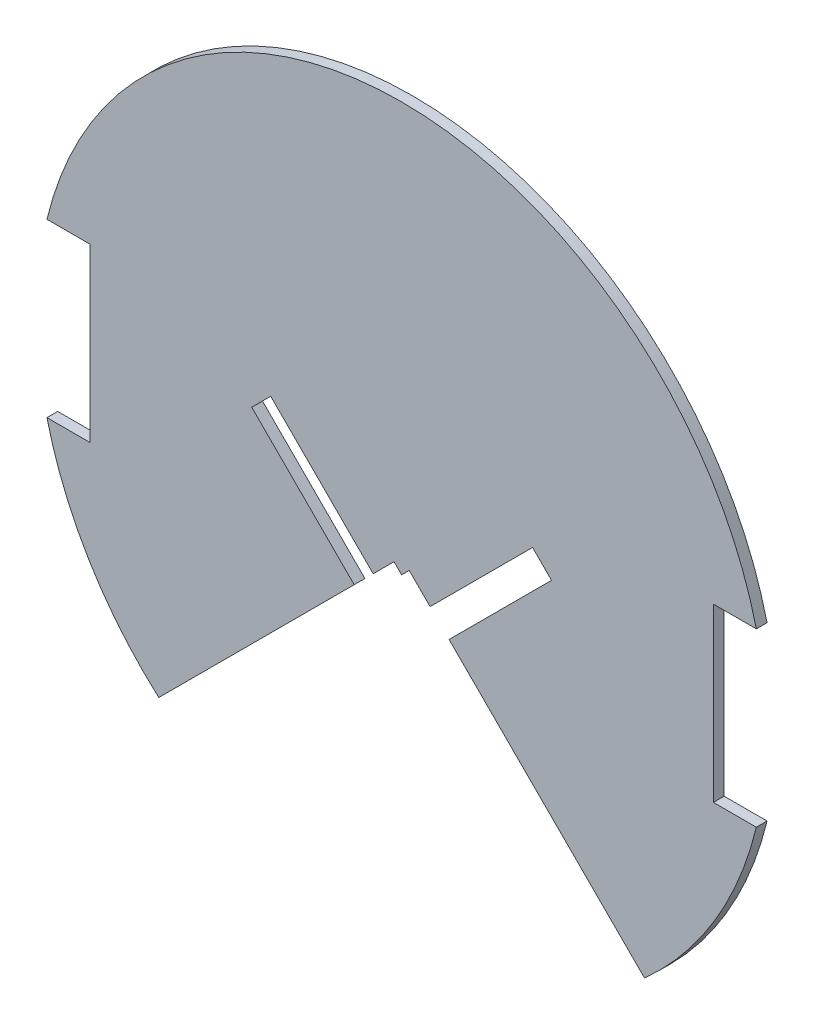
SolidWorks part; units mm, degrees
ref_plane "Front Plane" through (0, 0, 0) normal (0, 0, 1) x (1, 0, 0)
ref_plane "Top Plane" through (0, 0, 0) normal (0, 1, 0) x (1, 0, 0)
ref_plane "Right Plane" through (0, 0, 0) normal (1, 0, 0) x (0, 0, -1)
sketch "Sketch1" plane through (0, 0, 0) normal (0, 0, 1) x (1, 0, 0)
  circle A0 centre (0, 0) radius 215.9
  dimension "D1" = 431.8
extrude "Base Plate Extrusion" add sketch "Sketch1" along normal blind 6.35
sketch "Sketch2" plane through (0, 0, 6.35) normal (0, 0, 1) x (1, 0, 0)
  line L0 (0, 0) -> (0, -230.9791) construction
  line L1 (0, -17.4608) -> (143.6841, -161.1449)
  line L2 (0, -17.4608) -> (-143.6841, -161.1449)
  circle A1 centre (0, 0) radius 215.9 construction
  arc A2 (143.6841, -161.1449) -> (-143.6841, -161.1449) centre (0, 0) cw
  dimension "D1" = 90
  dimension "D2" = 203.2
extrude "V Funnel Cut" cut sketch "Sketch2" against normal through all
sketch "Sketch3" plane through (0, 0, 6.35) normal (0, 0, 1) x (1, 0, 0)
  line L0 (0, 0) -> (251.7982, 0) construction
  line L1 (209.8384, 50.8) -> (184.4384, 50.8)
  line L2 (209.8384, 50.8) -> (209.8384, -50.8)
  line L3 (209.8384, -50.8) -> (184.4384, -50.8)
  line L4 (184.4384, 50.8) -> (184.4384, -50.8)
  arc A0 (143.6841, -161.1449) -> (-143.6841, -161.1449) centre (0, 0) ccw construction
  arc A1 (209.8384, 50.8) -> (209.8384, -50.8) centre (0, 0) cw
  arc M7 (143.6841, -161.1449) -> (-143.6841, -161.1449) centre (0, 0) ccw
  dimension "D1" = 25.4
  dimension "D2" = 101.6
extrude "Wheel Track Cut" cut sketch "Sketch3" against normal through all contours L2 L0 A1 | L4 L0 L2 L1 | L0 L4 L3 L2 | L0 L2 M7 region at (197.1384, 25.4, 6.35) region at (197.1384, -25.4, 6.35) region at (212.266, 19.0862, 6.35) region at (212.266, -19.0862, 6.35)
mirror "Wheel Track Cut Mirror" about plane through (0, 0, 0) normal (1, 0, 0) of "Wheel Track Cut"
sketch "Sketch4" plane through (0, 0, 6.35) normal (0, 0, 1) x (1, 0, 0)
  line L0 (88.68, 15.0926) -> (77.4547, 26.3179)
  line L1 (88.68, 15.0926) -> (28.0633, -45.5241)
  line L2 (77.4547, 26.3179) -> (16.838, -34.2988)
  line L3 (28.0633, -45.5241) -> (16.838, -34.2988)
  line L4 (84.3174, 21.9553) -> (56.956, -5.4061) construction
  line L5 (65.1069, -1.7454) -> (69.5826, 2.7303) construction
  line L6 (65.0924, 7.2204) -> (60.6167, 2.7447) construction
  line L7 (143.6841, -161.1449) -> (0, -17.4608) construction
  dimension "D1" = 15.875
  dimension "D2" = 85.725
extrude "Cut-Extrude3" cut sketch "Sketch4" against normal through all
sketch "Sketch5" plane through (0, 0, 6.35) normal (0, 0, 1) x (1, 0, 0)
  line L0 (-4.4901, -21.951) -> (0, -17.4608)
  line L1 (-4.4901, -21.951) -> (0, -26.4411)
  line L2 (0, -17.4608) -> (4.4901, -21.951)
  line L3 (0, -26.4411) -> (4.4901, -21.951)
  line L4 (0, -17.4608) -> (-143.6841, -161.1449) construction
  line L5 (0, -26.4411) -> (-4.4901, -21.951) construction
  line L6 (4.4901, -21.951) -> (0, -26.4411) construction
extrude "Boss-Extrude2" add sketch "Sketch5" against normal up to surface (6.35 mm away) up to face at (14.0691, -14.8765, 0)
mirror "Mirror2" about plane through (0, 0, 0) normal (1, 0, 0) of "Cut-Extrude3"
